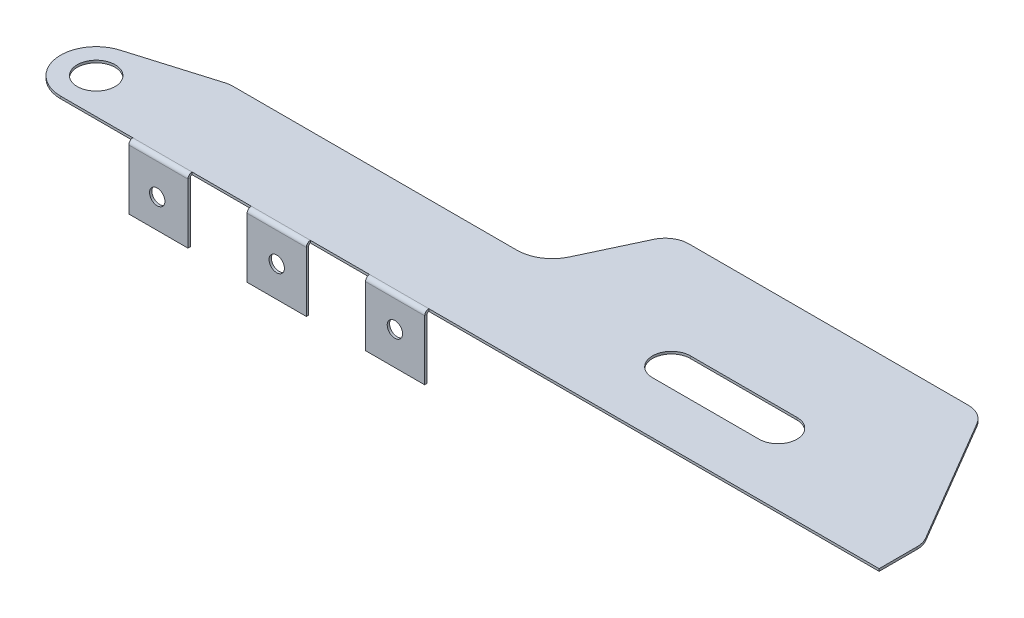
SolidWorks part; units mm, degrees
note: The reader was unsure of these and kept them because the rebuilt part matched: flange length of "Edge-Flange5", "Edge-Flange6", "Edge-Flange7".
ref_plane "Front Plane" through (0, 0, 0) normal (0, 0, 1) x (1, 0, 0)
ref_plane "Top Plane" through (0, 0, 0) normal (0, 1, 0) x (1, 0, 0)
ref_plane "Right Plane" through (0, 0, 0) normal (1, 0, 0) x (0, 0, -1)
sketch "Sketch2" plane through (0, 0, 0) normal (0, 1, 0) x (1, 0, 0)
  line L0 (-41.2984, 48.6341) -> (76.7016, 48.6341)
  line L1 (85.3182, 43.709) -> (116.3182, -8.9251)
  line L2 (117.7016, -14) -> (117.7016, -30)
  line L3 (117.7016, -30) -> (-228, -30)
  line L7 (-232.2984, -0.6291) -> (-198.164, 9.5806)
  line L8 (-195.2984, 10) -> (-75.2984, 10)
  line L9 (-61.7162, 18.6341) -> (-50.3532, 42.878)
  line L10 (0, 0) -> (45, 0) construction
  line L11 (0, 8) -> (45, 8)
  line L12 (0, -8) -> (45, -8)
  arc A0 (-232.2984, -0.6291) -> (-228, -30) centre (-228, -15) ccw
  arc A1 (-198.164, 9.5806) -> (-195.2984, 10) centre (-195.2984, 0) cw
  arc A2 (116.3182, -8.9251) -> (117.7016, -14) centre (107.7016, -14) cw
  arc A3 (76.7016, 48.6341) -> (85.3182, 43.709) centre (76.7016, 38.6341) cw
  arc A4 (-41.2984, 48.6341) -> (-50.3532, 42.878) centre (-41.2984, 38.6341) ccw
  arc A5 (-75.2984, 10) -> (-61.7162, 18.6341) centre (-75.2984, 25) ccw
  arc A6 (0, 8) -> (0, -8) centre (0, 0) ccw
  arc A7 (45, -8) -> (45, 8) centre (45, 0) ccw
  circle A8 centre (-228, -15) radius 8
  point P8 (0, 0)
  point P23 (22.5, 0)
  point P29 (0, 0)
  point P30 (0, 0)
  point P31 (0, 0)
  point P32 (0, 0)
  point P33 (0, 0)
  point P34 (0, 0)
  point P35 (0, 0)
  point P36 (0, 0)
  point P37 (0, 0)
  dimension "D1" = 10
  dimension "D2" = 15
  dimension "D8" = 15
  dimension "D9" = 8
  dimension "D15" = 16
  dimension "D3" = 34
  dimension "D4" = 120
  dimension "D5" = 118
  dimension "D6" = 41
  dimension "D7" = 37
  dimension "D10" = 45
  dimension "D11" = 10
  dimension "D12" = 30
  dimension "D13" = 25
  dimension "D14" = 16
  dimension "D16" = 228
base flange "Base-Flange1" sketch "Sketch2" thickness 1 reverse thickness direction no parameters "D1"=0.7366
edge flange "Edge-Flange5" sketch "Sketch22" flange angle 90 flange length 27 flange position bend outside bend radius 0.7366 thickness 1 relief rectangular parameters "D6"=10
sketch "Sketch22" plane through (0, -1, 30) normal (0, 0, -1) x (1, 0, 0)
  line L2 (-197.5, 0) -> (-197.5, 26)
  line L3 (-197.5, 26) -> (-172.5, 26)
  line L4 (-172.5, 26) -> (-172.5, 0)
  line L5 (117.7016, 0) -> (-228, 0) construction
  line L6 (-172.5, 0) -> (-197.5, 0)
  point P7 (-185, 26)
  dimension "D1" = 25
  dimension "D2" = 26
  dimension "D3" = 58
bend "EdgeBend5" bend radius 0.7366 bend angle 90 parameters "D5"=1
edge flange "Edge-Flange6" sketch "Sketch25" flange angle 90 flange length 27 flange position bend outside bend radius 0.7366 thickness 1 relief rectangular parameters "D6"=10
sketch "Sketch25" plane through (0, -1, 30) normal (0, 0, -1) x (1, 0, 0)
  line L2 (-147.5, 0) -> (-147.5, 26)
  line L3 (-147.5, 26) -> (-122.5, 26)
  line L4 (-122.5, 26) -> (-122.5, 0)
  line L5 (117.7016, 0) -> (-172.5, 0) construction
  line L6 (-122.5, 0) -> (-147.5, 0)
  line L7 (-172.5, 26) -> (-197.5, 26) construction
  point P6 (-135, 26)
  point P9 (-185, 26)
  dimension "D1" = 50
  dimension "D2" = 26
  dimension "D3" = 25
bend "EdgeBend6" bend radius 0.7366 bend angle 90 parameters "D5"=2
edge flange "Edge-Flange7" sketch "Sketch28" flange angle 90 flange length 27 flange position bend outside bend radius 0.7366 thickness 1 relief rectangular parameters "D6"=10
sketch "Sketch28" plane through (0, -1, 30) normal (0, 0, 1) x (-1, 0, 0)
  line L0 (122.5, 0) -> (-117.7016, 0) construction
  line L1 (97.5, 0) -> (72.5, 0)
  line L2 (72.5, 0) -> (72.5, 26)
  line L3 (72.5, 26) -> (97.5, 26)
  line L4 (97.5, 26) -> (97.5, 0)
  line L5 (122.5, 26) -> (147.5, 26) construction
  point P6 (85, 26)
  point P9 (135, 26)
  dimension "D1" = 50
  dimension "D2" = 25
  dimension "D3" = 26
bend "EdgeBend7" bend radius 0.7366 bend angle 90 parameters "D5"=3
sketch "Sketch29" plane through (0, 0, 31.7366) normal (0, 0, 1) x (1, 0, 0)
  line L0 (-97.5, 0) -> (-72.5, 0) construction
  line L1 (-147.5, -1) -> (-122.5, -1) construction
  line L2 (-172.5, -1.7366) -> (-197.5, -1.7366) construction
  circle A0 centre (-85.0823, -13) radius 3.25
  circle A1 centre (-135, -14) radius 3.25
  circle A2 centre (-185.4778, -14.7366) radius 3.25
  point P10 (-135, -1)
  dimension "D1" = 6.5
  dimension "D2" = 6.5
  dimension "D3" = 6.5
  dimension "D4" = 13
  dimension "D5" = 13
  dimension "D6" = 13
extrude "Cut-Extrude2" cut sketch "Sketch29" against normal blind 10 normal cut yes
sketch "Bend-Lines1" [suppressed] plane through (0, 0, 0) normal (0, 1, 0) x (1, 0, 0)
sketch "Bounding-Box1" [suppressed] plane through (0, 0, 0) normal (0, 1, 0) x (1, 0, 0)
sheet metal parameters "Sheet-Metal1" thickness 1 parameters "D1"=0.7366
flat pattern "Flat-Pattern1" [suppressed]
sketch "Bend-Lines2" plane through (0, 0, 0) normal (0, 1, 0) x (1, 0, 0)
sketch3d "Bounding-Box2" [suppressed]
  line L0 (-15, -15, 0) -> (345.7016, -15, 0) construction
  line L1 (-15, 63.6341, 0) -> (345.7016, 63.6341, 0) construction
  line L2 (-15, -15, 0) -> (-15, 63.6341, 0) construction
  line L3 (345.7016, -15, 0) -> (345.7016, 63.6341, 0) construction
sheet metal parameters "Sheet-Metal7" thickness 1 parameters "D1"=0.7366
flat pattern "Flat-Pattern1"
sketch "Bend-Lines2" plane through (0, 0, 0) normal (0, 1, 0) x (1, 0, 0)
  line L0 (-197.5, -30.9712) -> (-172.5, -30.9712) construction
  line L1 (-197.5, -30.9712) -> (-172.5, -30.9712) construction
sketch3d "Bounding-Box2" [suppressed]
  line L0 (347.2319, -14.8565, 0) -> (-10.5287, -48.3959, 0) construction
  line L1 (338.5351, 77.912, 0) -> (-19.2256, 44.3726, 0) construction
  line L2 (347.2319, -14.8565, 0) -> (338.5351, 77.912, 0) construction
  line L3 (-10.5287, -48.3959, 0) -> (-19.2256, 44.3726, 0) construction
bend of the flat pattern "Flatten-<EdgeBend5>1"
sheet metal parameters "Sheet-Metal8" thickness 1 parameters "D1"=0.7366
flat pattern "Flat-Pattern1"
sketch "Bend-Lines2" plane through (0, 0, 0) normal (0, 1, 0) x (1, 0, 0)
  line L0 (-197.5, -30.9712) -> (-172.5, -30.9712) construction
  line L1 (-197.5, -30.9712) -> (-172.5, -30.9712) construction
  line L2 (-147.5, -30.9712) -> (-122.5, -30.9712) construction
  line L3 (-147.5, -30.9712) -> (-122.5, -30.9712) construction
sketch3d "Bounding-Box2" [suppressed]
  line L0 (347.554, -14.7902, 0) -> (-8.8487, -55.1573, 0) construction
  line L1 (336.7394, 80.6916, 0) -> (-19.6632, 40.3246, 0) construction
  line L2 (347.554, -14.7902, 0) -> (336.7394, 80.6916, 0) construction
  line L3 (-8.8487, -55.1573, 0) -> (-19.6632, 40.3246, 0) construction
bend of the flat pattern "Flatten-<EdgeBend5>1"
bend of the flat pattern "Flatten-<EdgeBend6>1"
sheet metal parameters "Sheet-Metal9" thickness 1 parameters "D1"=0.7366
flat pattern "Flat-Pattern1"
sketch "Bend-Lines2" plane through (0, 0, 0) normal (0, 1, 0) x (1, 0, 0)
  line L0 (-197.5, -30.9712) -> (-172.5, -30.9712) construction
  line L1 (-197.5, -30.9712) -> (-172.5, -30.9712) construction
  line L2 (-147.5, -30.9712) -> (-122.5, -30.9712) construction
  line L3 (-147.5, -30.9712) -> (-122.5, -30.9712) construction
  line L4 (-97.5, -30.9712) -> (-72.5, -30.9712) construction
  line L5 (-97.5, -30.9712) -> (-72.5, -30.9712) construction
sketch3d "Bounding-Box2" [suppressed]
  line L0 (348.044, -14.665, 0) -> (-5.8152, -65.2799, 0) construction
  line L1 (333.8199, 84.7792, 0) -> (-20.0394, 34.1643, 0) construction
  line L2 (348.044, -14.665, 0) -> (333.8199, 84.7792, 0) construction
  line L3 (-5.8152, -65.2799, 0) -> (-20.0394, 34.1643, 0) construction
bend of the flat pattern "Flatten-<EdgeBend5>1"
bend of the flat pattern "Flatten-<EdgeBend6>1"
bend of the flat pattern "Flatten-<EdgeBend7>1"
sheet metal parameters "Sheet-Metal10" thickness 1 parameters "D1"=0.7366
flat pattern "Flat-Pattern1"
sketch "Bend-Lines2" plane through (0, 0, 0) normal (0, 1, 0) x (1, 0, 0)
  line L0 (-197.5, -30.9712) -> (-172.5, -30.9712) construction
  line L1 (-197.5, -30.9712) -> (-172.5, -30.9712) construction
  line L2 (-147.5, -30.9712) -> (-122.5, -30.9712) construction
  line L3 (-147.5, -30.9712) -> (-122.5, -30.9712) construction
  line L4 (-97.5, -30.9712) -> (-72.5, -30.9712) construction
  line L5 (-97.5, -30.9712) -> (-72.5, -30.9712) construction
sketch3d "Bounding-Box2" [suppressed]
  line L0 (348.044, -14.665, 0) -> (-5.8152, -65.2799, 0) construction
  line L1 (333.8199, 84.7792, 0) -> (-20.0394, 34.1643, 0) construction
  line L2 (348.044, -14.665, 0) -> (333.8199, 84.7792, 0) construction
  line L3 (-5.8152, -65.2799, 0) -> (-20.0394, 34.1643, 0) construction
bend of the flat pattern "Flatten-<EdgeBend5>1"
bend of the flat pattern "Flatten-<EdgeBend6>1"
bend of the flat pattern "Flatten-<EdgeBend7>1"
